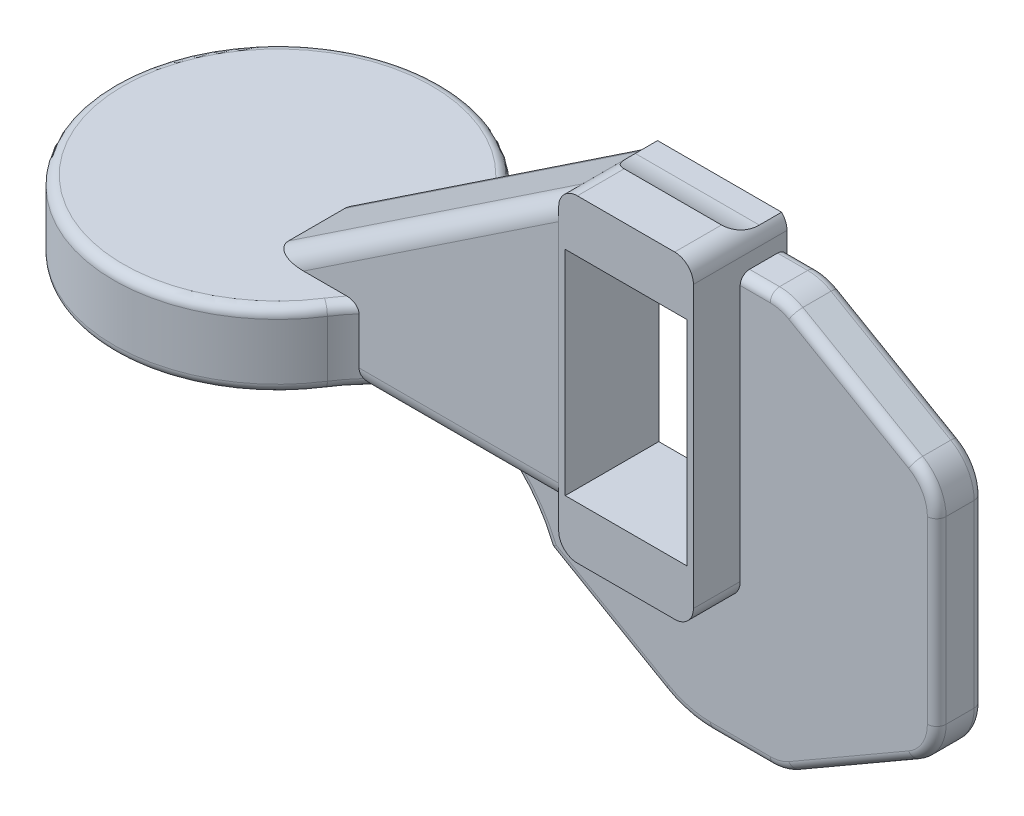
SolidWorks part; units mm, degrees
material "ABS"
ref_plane "Front Plane" through (0, 0, 0) normal (0, 0, 1) x (1, 0, 0)
ref_plane "Top Plane" through (0, 0, 0) normal (0, 1, 0) x (1, 0, 0)
ref_plane "Right Plane" through (0, 0, 0) normal (1, 0, 0) x (0, 0, -1)
other "Center of Mass"
sketch "Sketch1" plane through (0, 0, 0) normal (0, 1, 0) x (1, 0, 0)
  line L0 (0, 0) -> (128.1157, 0) construction
  line L2 (27.3861, -2.5) -> (82.5, -2.5)
  line L4 (27.3861, 2.5) -> (82.5, 2.5)
  line L5 (82.5, -2.5) -> (82.5, 2.5)
  arc A0 (14.7464, 9.4231) -> (14.7464, -9.4231) centre (0, 0) ccw
  arc A1 (27.3861, 2.5) -> (14.7464, 9.4231) centre (27.3861, 17.5) cw
  arc A2 (14.7464, -9.4231) -> (27.3861, -2.5) centre (27.3861, -17.5) cw
  point P3 (50, 0)
  dimension "D1" = 35
  dimension "D4" = 15
  dimension "D5" = 15
  dimension "D2" = 5
  dimension "D3" = 82.5
extrude "Boss-Extrude1" add sketch "Sketch1" along normal blind 8
sketch "Sketch4" plane through (82.5, 0, 0) normal (1, 0, 0) x (0, 0, -1)
  line L0 (0, 8) -> (0, 0) construction
  line L1 (-2.5, 8) -> (2.5, 8) construction
  line L3 (-2.5, -21) -> (2.5, -21)
  line L4 (-2.5, -21) -> (-2.5, 29)
  line L5 (-2.5, 29) -> (2.5, 29)
  line L6 (2.5, -21) -> (2.5, 29)
  line L7 (-2.5, -21) -> (2.5, 29) construction
  line L8 (-2.5, 29) -> (2.5, -21) construction
  point P5 (0, 4)
  dimension "D1" = 50
  dimension "D2" = 5
extrude "Boss-Extrude4" add sketch "Sketch4" against normal blind 50
fillet "Fillet1" radius 15 2 edges at (32.5, 0, 0) (32.5, 8, 0)
sketch "Sketch5" plane through (0, 0, 2.5) normal (0, 0, 1) x (1, 0, 0)
  line L0 (82.5, 4) -> (27.3861, 4) construction
  line L1 (82.5, 29) -> (82.5, -21) construction
  line L2 (27.3861, 11.7188) -> (27.3861, -3.7188) construction
  line L3 (57.5, 29) -> (57.5, -21) construction
  line L4 (32.5, 29) -> (82.5, 29) construction
  line L5 (32.5, -21) -> (82.5, -21) construction
  line L6 (54.9431, 4) -> (27.3861, 4) construction
  line L7 (32.5, 29) -> (32.5, 23) construction
  line L8 (32.5, 30.25) -> (57, 30.25)
  line L9 (32.5, 30.25) -> (32.5, -22.25)
  line L10 (32.5, -22.25) -> (57, -22.25)
  line L11 (57, 30.25) -> (57, -22.25)
  line L12 (32.5, 30.25) -> (57, -22.25) construction
  line L13 (32.5, -22.25) -> (57, 30.25) construction
  line L14 (44.75, -22.25) -> (44.75, 30.25) construction
  line L15 (38.25, 1.2) -> (51.25, 24) construction
  line L16 (38.25, 24) -> (51.25, 24)
  line L17 (38.25, 24) -> (38.25, 1.2)
  line L18 (38.25, 1.2) -> (51.25, 1.2)
  line L19 (51.25, 24) -> (51.25, 1.2)
  line L20 (38.25, 12.6) -> (51.25, 12.6) construction
  line L21 (51.95, -4.4) -> (37.55, -4.4)
  line L22 (51.95, -4.4) -> (51.95, 29.6)
  line L23 (51.95, 29.6) -> (37.55, 29.6)
  line L24 (37.55, -4.4) -> (37.55, 29.6)
  line L25 (51.95, -4.4) -> (37.55, 29.6) construction
  line L26 (51.95, 29.6) -> (37.55, -4.4) construction
  circle A0 centre (44.75, 18) radius 12.25
  circle A1 centre (44.75, -10) radius 12.25
  circle A2 centre (44.75, -10) radius 15.75
  circle A3 centre (64.9562, -1.2988) radius 1.5
  circle A4 centre (64.9562, -1.2988) radius 3
  circle A5 centre (64.9562, 9.2988) radius 3
  circle A6 centre (64.9562, 9.2988) radius 1.5
  circle A7 centre (44.75, -10) radius 1.5
  circle A8 centre (44.75, -10) radius 3
  point P13 (44.75, 4)
  point P30 (44.75, 12.6)
  dimension "D4" = 12.25
  dimension "D5" = 24.5
  dimension "D13" = 31.5
  dimension "D14" = 3
  dimension "D16" = 6
  dimension "D17" = 22
  dimension "D18" = 3
  dimension "D19" = 6
  dimension "D1" = 24.5
  dimension "D2" = 52.5
  dimension "D3" = 0
  dimension "D6" = 12.25
  dimension "D7" = 6
  dimension "D8" = 22.8
  dimension "D9" = 13
  dimension "D10" = 34
  dimension "D11" = 14.4
  dimension "D12" = 5.6
  dimension "D15" = 5.2988
sketch "Sketch6" plane through (0, 0, 2.5) normal (0, 0, 1) x (1, 0, 0)
  circle A0 centre (44.75, -10) radius 1.5
  dimension "D1" = 3
sketch "Sketch8" plane through (0, 0, 2.5) normal (0, 0, 1) x (1, 0, 0)
  line L0 (37.55, -4.4) -> (37.55, 29.6)
  line L1 (37.55, 29.6) -> (51.95, 29.6)
  line L2 (51.95, 29.6) -> (51.95, -4.4)
  line L3 (51.95, -4.4) -> (37.55, -4.4)
  dimension "D1" = 34
extrude "Boss-Extrude5" add sketch "Sketch8" along normal blind 5
sketch "Sketch9" plane through (0, 0, 7.5) normal (0, 0, 1) x (1, 0, 0)
  line L0 (38.25, 24) -> (51.25, 24)
  line L1 (51.25, 24) -> (51.25, 1.2)
  line L2 (51.25, 1.2) -> (38.25, 1.2)
  line L3 (38.25, 1.2) -> (38.25, 24)
extrude "Cut-Extrude2" cut sketch "Sketch9" against normal through all
fillet "Fillet2" radius 5 2 edges at (32.5, -21, 0) (32.5, 29, 0)
fillet "Fillet3" radius 2 4 edges at (51.95, -4.4, 5) (51.95, 29.6, 5) (37.55, 29.6, 5) (37.55, -4.4, 5)
fillet "Fillet4" radius 6 1 edges at (44.75, 29, 2.5)
sketch "Sketch14" plane through (0, 0, 2.5) normal (0, 0, 1) x (1, 0, 0)
  line L0 (72.9562, 29) -> (72.9562, -21)
  line L1 (82.5, -21) -> (28.5, -21)
  line L2 (82.5, -21) -> (82.5, -19.5)
  line L3 (56.5017, -18) -> (28.5, -18)
  line L4 (28.5, -21) -> (28.5, -18)
  line L5 (51.3783, 29) -> (82.5, 29) construction
  line L6 (56.5017, 26) -> (28.5, 26)
  line L7 (82.5, 4) -> (14.7464, 4) construction
  line L8 (14.7464, 8) -> (14.7464, 0) construction
  line L9 (51.3055, 29) -> (29.6549, 16.5)
  line L10 (29.6549, 16.5) -> (29.6549, -8.5)
  line L11 (29.6549, -8.5) -> (51.3055, -21)
  line L12 (51.3055, -21) -> (72.9562, -8.5)
  line L13 (72.9562, -8.5) -> (72.9562, 16.5)
  line L14 (72.9562, 16.5) -> (51.3055, 29)
  circle A0 centre (51.3055, 4) radius 21.6506 construction
  circle A1 centre (64.9562, 9.2988) radius 3 construction
  line M5 (32.5, -15) -> (32.5, -16)
  arc M6 (32.5, -16) -> (37.5, -21) centre (37.5, -16) ccw
  line M7 (37.5, -21) -> (82.5, -21)
  line M8 (82.5, -21) -> (82.5, 29)
  line M9 (82.5, 29) -> (51.3783, 29)
  arc M10 (51.3783, 29) -> (51.95, 27.6) centre (49.95, 27.6) cw
  line M11 (51.95, 27.6) -> (51.95, -2.4)
  line M15 (37.55, -2.4) -> (37.55, 27.6)
  arc M16 (37.55, 27.6) -> (38.1217, 29) centre (39.55, 27.6) cw
  line M17 (38.1217, 29) -> (37.5, 29)
  arc M18 (37.5, 29) -> (32.5, 24) centre (37.5, 24) ccw
  line M19 (32.5, 24) -> (32.5, 23)
  arc M20 (32.5, 23) -> (27.3861, 11.7188) centre (17.5, 23) cw
  arc M24 (27.3861, -3.7188) -> (32.5, -15) centre (17.5, -15) cw
  dimension "D4" = 8
  dimension "D6" = 25
  dimension "D1" = 3
  dimension "D2" = 8
  dimension "D3" = 54
  dimension "D5" = 0
extrude "Cut-Extrude6" cut sketch "Sketch14" against normal blind 10 contours L11 L3 M24 M5 M6 | L11 L3 M6 M7 | L12 L1 L0 | L11 L12 L3 | L0 M9 M7 M8 | L14 L0 M9 M10 | L6 L14 M10 M11 | L9 L6 M15 M18 M19 M20 | L6 M15 M16 M17 M18 region at (77.7281, 4, 2.5) region at (65.7396, 24.8332, 2.5) region at (65.7393, -16.8333, 2.5) region at (53.4314, 26.9107, 2.5) region at (51.3055, -19, 2.5) region at (41.4922, -19.5298, 2.5) region at (36.9232, -15.2513, 2.5) region at (34.7312, 22.5576, 2.5) region at (35.7594, 27.2757, 2.5)
fillet "Fillet5" radius 5 4 edges at (56.5017, 26, 0) (72.9562, 16.5, 0) (72.9562, -8.5, 0) (56.5017, -18, 0)
fillet "Fillet6" radius 10 1 edges at (46.1094, -18, 0)
ref_plane "Plane5" through (0, 0, 0) normal (0, 0, 1) x (1, 0, 0)
sketch "Sketch18" plane through (0, 0, 0) normal (0, 0, 1) x (1, 0, 0)
  line L0 (6.6848, 8) -> (6.6848, 0)
  line L1 (-17.5, 0) -> (14.7464, 0) construction
  line L2 (14.7464, 8) -> (-1.3768, 8) construction
  line L3 (6.6848, 0) -> (17.5, 0)
  line L4 (17.5, 0) -> (37.55, 0)
  line L5 (37.55, 21.0582) -> (37.55, -2.4) construction
  line L6 (37.55, 0) -> (37.55, 27.6)
  line L7 (14.7464, 8) -> (-17.5, 8) construction
  line L8 (-1.3768, 8) -> (-1.3768, 17.551) construction
  line L9 (-1.3768, 17.551) -> (14.7464, 17.551) construction
  line L10 (14.7464, 17.551) -> (14.7464, 8) construction
  line L11 (6.6848, 17.551) -> (6.6848, -15.9983) construction
  line L12 (38.1217, 29) -> (6.6848, 8)
  arc A0 (37.55, 27.6) -> (38.1217, 29) centre (39.55, 27.6) cw
  dimension "D1" = 17.551
extrude "Boss-Extrude7" add sketch "Sketch18" along normal blind 7.5 and the other way blind 2.5 separate body
fillet "Fillet7" radius 2 1 edges at (22.4032, 18.5, 7.5)
fillet "Fillet8" radius 2 1 edges at (22.4032, 18.5, -2.5)
fillet "Fillet9" radius 2 1 edges at (22.1174, 0, 7.5)
fillet "Fillet10" radius 1 29 edges at (53.556, 26, -2.5) (56.456, 25.8296, -2.5) (64.0591, 21.6368, -2.5) (72.2863, 16.1132, -2.5) (72.9562, 4, -2.5) (72.2863, -8.1132, -2.5) (64.0591, -13.6368, -2.5) (56.456, -17.8296, -2.5) (51.9754, -18, -2.5) (46.2007, -17.6593, -2.5) (53.556, 26, 2.5) (56.456, 25.8296, 2.5) (64.0591, 21.6368, 2.5) (72.2863, 16.1132, 2.5) (72.9562, 4, 2.5) (72.2863, -8.1132, 2.5) (64.0591, -13.6368, 2.5) (56.456, -17.8296, 2.5) (51.9754, -18, 2.5) (46.2007, -17.6593, 2.5) (29.7819, -6.3887, -2.5) (24.1319, -1.5457, -2.8573) (16.0098, 0, -7.7235) (-17.5, 0, 0) (16.0098, 0, 7.7235) (20.7542, -0.3573, 4.0457) (37.6321, -13.1056, -2.5) (37.6321, -13.1056, 2.5) (29.7819, -6.3887, 2.5)
fillet "Fillet11" radius 1 7 edges at (29.7819, 14.3887, -2.5) (20.7542, 8.3573, -4.0457) (16.0098, 8, -7.7235) (29.7819, 14.3887, 2.5) (24.1319, 9.5457, 2.8573) (16.0098, 8, 7.7235) (-17.5, 8, 0)
